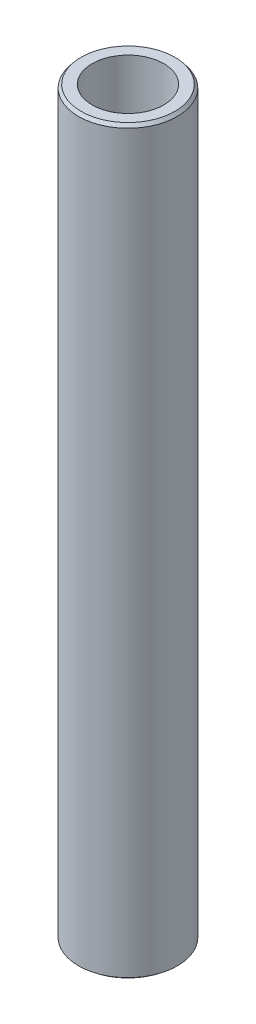
SolidWorks part; units mm, degrees
ref_plane "Front Plane" through (0, 0, 0) normal (0, 0, 1) x (1, 0, 0)
ref_plane "Top Plane" through (0, 0, 0) normal (0, 1, 0) x (1, 0, 0)
ref_plane "Right Plane" through (0, 0, 0) normal (1, 0, 0) x (0, 0, -1)
sketch "Sketch1" plane through (0, 0, 0) normal (0, 1, 0) x (1, 0, 0)
  circle A0 centre (0, 0) radius 40
  dimension "SHAFT_OD" = 80
extrude "Boss-Extrude1" add sketch "Sketch1" along normal blind 600
sketch "Sketch2" plane through (0, 0, 0) normal (0, 1, 0) x (1, 0, 0)
  circle A0 centre (0, 0) radius 28.9978
  dimension "BORE_D" = 57.9957
extrude "Cut-Extrude1" cut sketch "Sketch2" along normal through all
chamfer "Chamfer1" distance 2.5511 angle 38.521 2 edges at (0, 600, 40) (0, 0, 40) first distance on face at (0, 600, 40) first distance on face at (0, 0, 28.9978)
